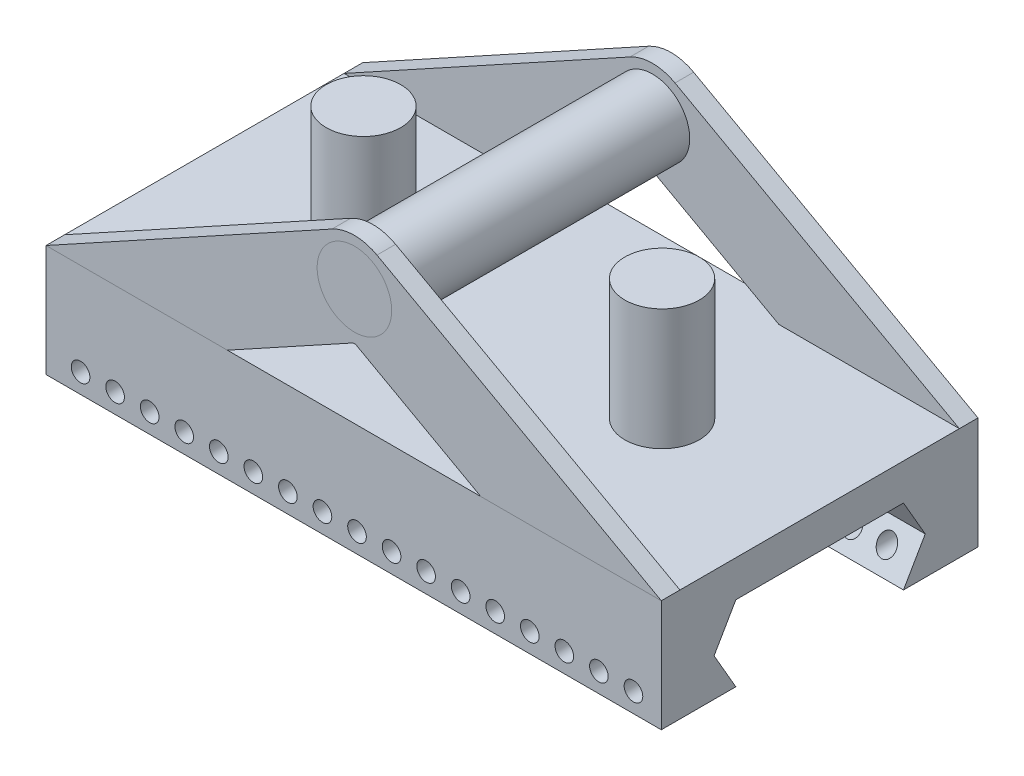
SolidWorks part; units mm, degrees
ref_plane "Front Plane" through (0, 0, 0) normal (0, 0, 1) x (1, 0, 0)
ref_plane "Top Plane" through (0, 0, 0) normal (0, 1, 0) x (1, 0, 0)
ref_plane "Right Plane" through (0, 0, 0) normal (1, 0, 0) x (0, 0, -1)
sketch "Sketch1" plane through (0, 0, 0) normal (0, 1, 0) x (1, 0, 0)
  line L0 (-31.9787, 0) -> (0.0813, 0) construction
  circle A0 centre (-31.9787, 0) radius 4
  circle A1 centre (0.0813, 0) radius 4
  dimension "D1" = 8
  dimension "D2" = 32.06
extrude "Boss-Extrude3" add sketch "Sketch1" along normal blind 13 and the other way blind 3 contours A0 | A1
sketch "Sketch3" plane through (0, 0, 0) normal (1, 0, 0) x (0, 0, -1)
  line L0 (0, 0) -> (-17, 0) construction
  line L1 (0, 0) -> (17, 0) construction
  line L2 (-17, 0) -> (-17, -12)
  line L3 (-17, -12) -> (-9, -12)
  line L4 (17, -12) -> (17, 0)
  line L5 (17, 0) -> (-17, 0)
  line L6 (-4, -3) -> (4, -3) construction
  line L8 (-9, -12) -> (-11.335, -7.9557)
  line L9 (-11.335, -7.9557) -> (-9, -3.9113)
  line L10 (-9, -3.9113) -> (9, -3.9113)
  line L11 (9, -3.9113) -> (11.335, -7.9557)
  line L12 (11.335, -7.9557) -> (9, -12)
  line L13 (9, -12) -> (17, -12)
  dimension "D1" = 34
  dimension "D2" = 17
  dimension "D3" = 12
  dimension "D4" = 120
  dimension "D5" = 120
  dimension "D6" = 120
  dimension "D7" = 120
  dimension "D10" = 4.67
sketch "Sketch4" plane through (0, 0, 0) normal (0, 0, 1) x (1, 0, 0)
  line L0 (-31.9787, 0) -> (0.0813, 0) construction
  circle A0 centre (-15.9487, 12.5) radius 4
  point P6 (-15.9487, 0)
  dimension "D1" = 8
  dimension "D2" = 12.5
extrude "Boss-Extrude4" add sketch "Sketch4" along normal blind 17 and the other way blind 17 separate body contours A0
ref_plane "Plane1" through (0, 0, 17) normal (0, 0, 1) x (1, 0, 0)
extrude "Boss-Extrude5" add sketch "Sketch3" along normal blind 17 and the other way blind 49.06 contours L5 L2 L3 L8 L9 L10 L11 L12 L13 L4
sketch "Sketch6" plane through (0, 0, 17) normal (0, 0, 1) x (1, 0, 0)
  line L3 (-31.9787, 0) -> (0.0813, 0) construction
  line L5 (4.0813, 0) -> (-3.9187, 0) construction
  line L6 (-18.3578, 16.8814) -> (-49.06, 0)
  line L7 (-49.06, 0) -> (-29.589, 0)
  line L8 (-2.3807, 0) -> (17, 0)
  line L9 (-13.5298, 16.876) -> (17, 0)
  line L10 (-15.9487, 7.5) -> (-29.589, 0)
  line L11 (-15.9487, 7.5) -> (-2.3807, 0)
  arc A2 (-13.5298, 16.876) -> (-18.3578, 16.8814) centre (-15.9487, 12.5) ccw
  dimension "D1" = 10
extrude "Boss-Extrude6" add sketch "Sketch6" against normal blind 2 separate body contours L8 L9 A2 L6 L7 L10 L11
ref_plane "Plane2" through (0, 0, -17) normal (0, 0, -1) x (-1, 0, 0)
sketch "Sketch8" plane through (0, 0, -17) normal (0, 0, -1) x (-1, 0, 0)
  line L0 (13.5298, 16.876) -> (-17, 0)
  line L1 (18.3578, 16.8814) -> (49.06, 0)
  line L2 (49.06, -12) -> (49.06, 0) construction
  line L3 (49.06, 0) -> (-17, 0) construction
  line L4 (15.9487, 7.5) -> (29.589, 0)
  line L5 (31.9787, 0) -> (-0.0813, 0) construction
  line L6 (15.9487, 7.5) -> (2.3807, 0)
  line L7 (-17, 0) -> (2.3807, 0)
  line L8 (29.589, 0) -> (49.06, 0)
  arc A0 (18.3578, 16.8814) -> (13.5298, 16.876) centre (15.9487, 12.5) ccw
  dimension "D1" = 10
extrude "Boss-Extrude8" add sketch "Sketch8" against normal blind 2 contours L1 L8 L4 L6 L7 L0 A0
extrude "Cut-Extrude1" cut sketch "Sketch4<3>" against normal through all both and the other way through all contours A0
sketch "Sketch4<3>" plane through (0, 0, 0) normal (0, 0, 1) x (1, 0, 0) same geometry as "Sketch4"
fillet "Fillet1" radius 0.5 1 edges at (-15.9487, 7.5, -16)
fillet "Fillet2" radius 0.5 1 edges at (-15.9487, 7.5, 16)
sketch "Sketch9" plane through (0, 0, 0) normal (0, 0, 1) x (1, 0, 0)
  line L0 (-49.06, 0) -> (-49.06, -12) construction
  line L1 (17, 0) -> (17, -12) construction
  line L2 (-49.06, -12) -> (17, -12) construction
  circle A0 centre (-45.35, -9.9) radius 1
  circle A1 centre (-37.93, -9.9) radius 1
  circle A2 centre (-23.09, -9.9) radius 1
  circle A3 centre (-15.67, -9.9) radius 1
  circle A4 centre (-41.64, -9.9) radius 1
  circle A5 centre (-30.51, -9.9) radius 1
  circle A6 centre (-19.38, -9.9) radius 1
  circle A7 centre (-34.22, -9.9) radius 1
  circle A8 centre (-26.8, -9.9) radius 1
  circle A9 centre (-11.96, -9.9) radius 1
  circle A10 centre (-8.25, -9.9) radius 1
  circle A11 centre (-4.54, -9.9) radius 1
  circle A12 centre (-0.83, -9.9) radius 1
  circle A13 centre (2.88, -9.9) radius 1
  circle A14 centre (6.59, -9.9) radius 1
  circle A15 centre (10.3, -9.9) radius 1
  circle A16 centre (14.01, -9.9) radius 1
  dimension "D2" = 2
  dimension "D1" = 66.06
  dimension "D3" = 2.1
  dimension "D4" = 3.71
  dimension "D5" = 3.71
  dimension "D6" = 3.71
  dimension "D7" = 3.71
  dimension "D8" = 3.71
  dimension "D9" = 3.71
  dimension "D10" = 3.71
  dimension "D11" = 3.71
  dimension "D12" = 3.71
  dimension "D13" = 3.71
  dimension "D14" = 3.71
  dimension "D15" = 3.71
  dimension "D16" = 3.71
  dimension "D17" = 3.71
  dimension "D18" = 3.71
  dimension "D19" = 3.71
  dimension "D20" = 3.71
extrude "Cut-Extrude2" cut sketch "Sketch9" against normal through all both and the other way through all
